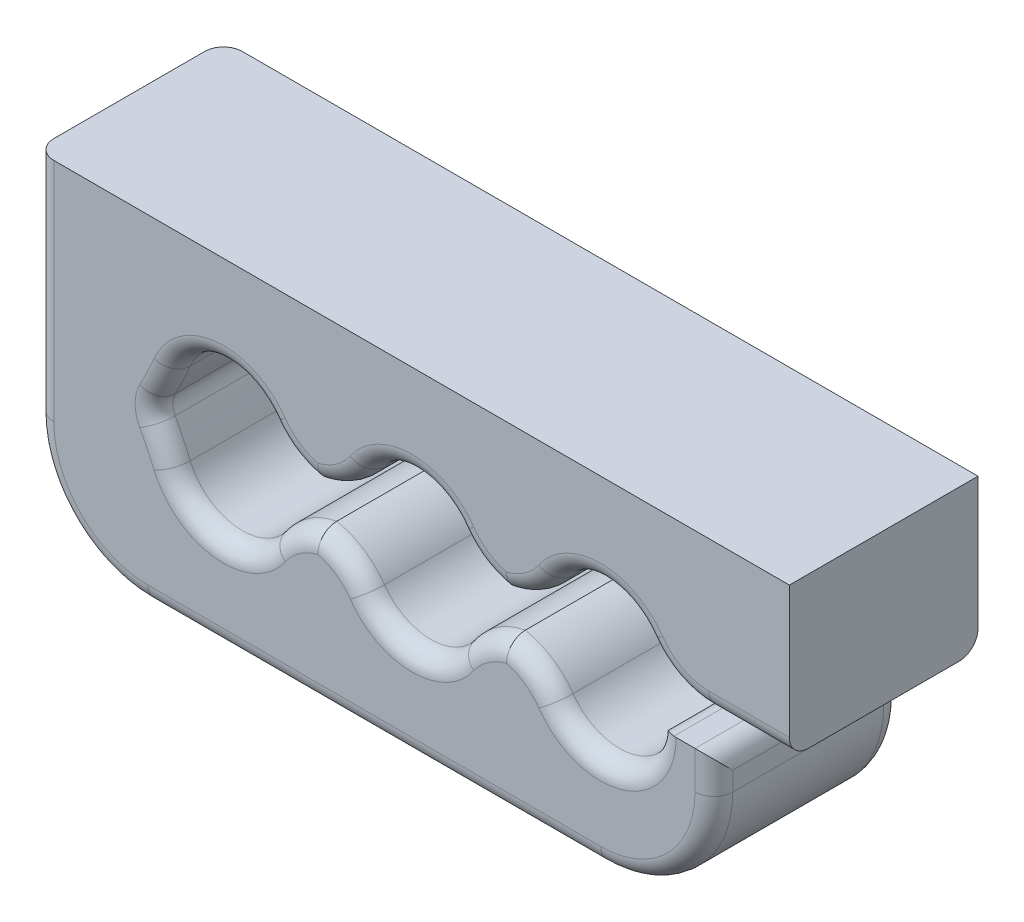
SolidWorks part; units mm, degrees
ref_plane "Front Plane" through (0, 0, 0) normal (0, 0, 1) x (1, 0, 0)
ref_plane "Top Plane" through (0, 0, 0) normal (0, 1, 0) x (1, 0, 0)
ref_plane "Right Plane" through (0, 0, 0) normal (1, 0, 0) x (0, 0, -1)
ref_axis "Axis1" through (0, 0, -88.99) along (0, 0, 1)
ref_axis "Axis2" through (-88.99, 0, 0) along (1, 0, 0)
ref_axis "Axis3" through (0, -55, 0) along (0, 1, 0)
sketch "Sketch3" plane through (0, 0, 0) normal (0, 0, 1) x (1, 0, 0)
  line L0 (-88.99, 0) -> (88.99, 0) construction
  line L4 (-20, 0) -> (-20, -4)
  line L5 (-20, -4) -> (-2, -4)
  line L7 (-13.5, 0) -> (-11.5, 0)
  line L8 (-8.5, 0) -> (-6.5, 0)
  line L9 (0, -55) -> (0, 55) construction
  line L10 (-2, -4) -> (-2, 0)
  line L11 (-3.5, 0) -> (-2, 0)
  line L12 (-20, 0.5) -> (0, 0.5) construction
  line L13 (-3.5, 1) -> (-2, 1)
  line L15 (-8.5, 1) -> (-6.5, 1)
  line L16 (-13.5, 1) -> (-11.5, 1)
  line L17 (-20, 5) -> (-2, 5)
  line L18 (-20, 1) -> (-20, 5)
  line L20 (-20, 1) -> (-20, 0)
  line L23 (-2, 5) -> (0, 5)
  line L24 (0, 5) -> (0, 1)
  line L25 (0, 1) -> (-2, 1)
  arc A0 (-6.5, 0) -> (-3.5, 0) centre (-5, 0) ccw
  arc A1 (-11.5, 0) -> (-8.5, 0) centre (-10, 0) ccw
  arc A2 (-16.5, 0) -> (-13.5, 0) centre (-15, 0) ccw
  arc A3 (-16.5, 1) -> (-13.5, 1) centre (-15, 1) cw
  arc A4 (-11.5, 1) -> (-8.5, 1) centre (-10, 1) cw
  arc A5 (-6.5, 1) -> (-3.5, 1) centre (-5, 1) cw
  arc A6 (-16.5, 1) -> (-16.5, 0) centre (-16.3087, 0.5) ccw
  point P0 (0, 0)
  dimension "D2" = 5
  dimension "D1" = 4
  dimension "D3" = 2
  dimension "D5" = 0.5
  dimension "D4" = 3
extrude "Boss-Extrude1" add sketch "Sketch3" along normal mid plane 5
fillet "Fillet1" radius 10 2 edges at (-16.5, 1, 0) (-16.5, 0, 0)
fillet "Fillet2" radius 2 9 edges at (-13.5, 1, 0) (-11.5, 1, 0) (-8.5, 1, 0) (-6.5, 1, 0) (-3.5, 1, 0) (-6.5, 0, 0) (-8.5, 0, 0) (-11.5, 0, 0) (-13.5, 0, 0)
fillet "Fillet3" radius 3 2 edges at (-20, -4, 0) (-2, -4, 0)
fillet "Fillet4" radius 0.5 50 edges at (-13.2152, -0.3215, -2.5) (-13.2152, 1.3215, -2.5) (-15.155, 2.492, -2.5) (-16.5709, 1.1651, -2.5) (-16.8441, 0.5, -2.5) (-16.5709, -0.1651, -2.5) (-13.2152, -0.3215, 2.5) (-13.2152, 1.3215, 2.5) (-15.155, 2.492, 2.5) (-16.5709, 1.1651, 2.5) (-16.8441, 0.5, 2.5) (-16.5709, -0.1651, 2.5) (-11.7848, 1.3215, -2.5) (-8.2152, 1.3215, -2.5) (-1.0639, 1, -2.5) (-6.7848, 1.3215, -2.5) (-5, 2.5, -2.5) (-8.2152, -0.3215, -2.5) (-11.7848, -0.3215, -2.5) (-6.7848, -0.3215, -2.5) (-6.7848, 1.3215, 2.5) (-1.0639, 1, 2.5) (-3.0535, 1.2272, 2.5) (-11.7848, 1.3215, 2.5) (-8.2152, 1.3215, 2.5) (-6.7848, -0.3215, 2.5) (-8.2152, -0.3215, 2.5) (-11.7848, -0.3215, 2.5) (-2, -0.5, -2.5) (-2.8787, -3.1213, -2.5) (-11, -4, -2.5) (-19.1213, -3.1213, -2.5) (-2, -0.5, 2.5) (-2.8787, -3.1213, 2.5) (-11, -4, 2.5) (-19.1213, -3.1213, 2.5) (-15.155, -1.492, -2.5) (-15.155, -1.492, 2.5) (-10, 2.5, -2.5) (-3.0535, 1.2272, -2.5) (-10, -1.5, -2.5) (-4.5508, -1.4312, -2.5) (-5, 2.5, 2.5) (-10, 2.5, 2.5) (-4.5508, -1.4312, 2.5) (-10, -1.5, 2.5) (-3.5, 0, 0) (-2, 0, 0) (-20, 2, -2.5) (-20, 2, 2.5)
